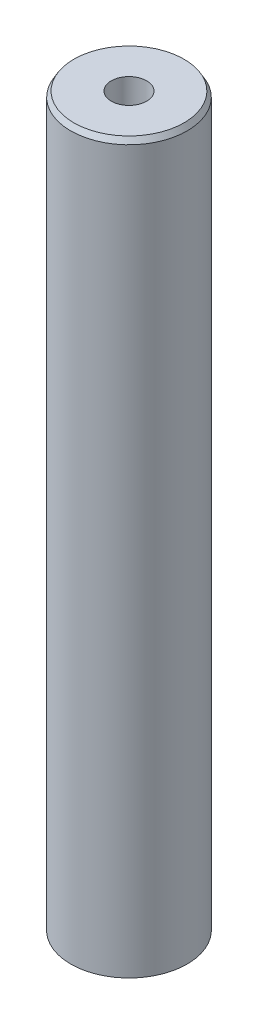
SolidWorks part; units mm, degrees
ref_plane "Front Plane" through (0, 0, 0) normal (0, 0, 1) x (1, 0, 0)
ref_plane "Top Plane" through (0, 0, 0) normal (0, 1, 0) x (1, 0, 0)
ref_plane "Right Plane" through (0, 0, 0) normal (1, 0, 0) x (0, 0, -1)
sketch "Sketch1" plane through (0, 0, 0) normal (0, 1, 0) x (1, 0, 0)
  circle A0 centre (0, 0) radius 35
  dimension "SHAFT_OD" = 70
extrude "Boss-Extrude1" add sketch "Sketch1" along normal blind 438.7415
sketch "Sketch2" plane through (0, 0, 0) normal (0, 1, 0) x (1, 0, 0)
  circle A0 centre (0, 0) radius 10.6328
  dimension "BORE_D" = 21.2655
extrude "Cut-Extrude1" cut sketch "Sketch2" along normal through all
chamfer "Chamfer1" distance 3.2596 angle 30 2 edges at (0, 438.7415, 35) (0, 0, 35) first distance on face at (0, 438.7415, 35) first distance on face at (0, 0, 10.6328)
